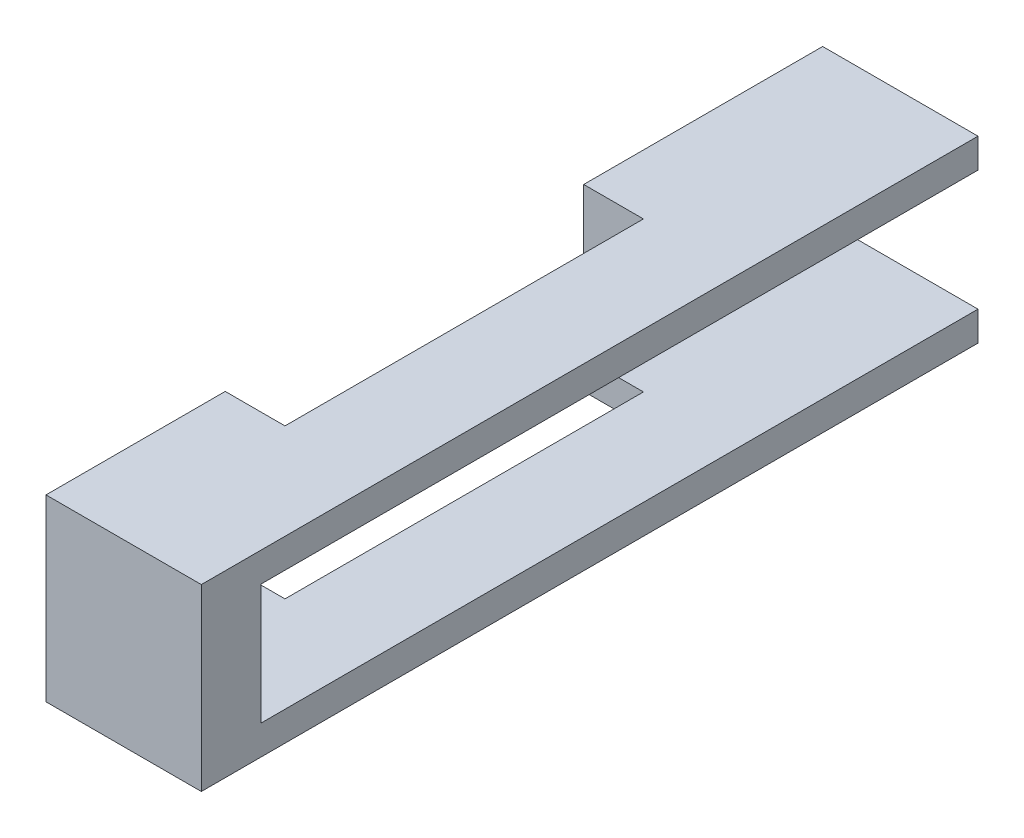
SolidWorks part; units mm, degrees
ref_plane "前视基准面" through (0, 0, 0) normal (0, 0, 1) x (1, 0, 0)
ref_plane "上视基准面" through (0, 0, 0) normal (0, 1, 0) x (1, 0, 0)
ref_plane "右视基准面" through (0, 0, 0) normal (1, 0, 0) x (0, 0, -1)
other "Configuration Table"
sketch "草图1" plane through (0, 0, 0) normal (0, 1, 0) x (1, 0, 0)
  line L1 (-15, 15) -> (15, 15)
  line L2 (-15, 15) -> (-15, -15)
  line L3 (-15, -15) -> (15, -15)
  line L4 (15, 15) -> (15, -15)
  line L5 (-15, 15) -> (15, -15) construction
  line L6 (-15, -15) -> (15, 15) construction
  point P0 (0, 0)
  dimension "D1" = 30
  dimension "D2" = 30
extrude "凸台-拉伸1" add sketch "草图1" along normal blind 30
sketch "草图2" plane through (15, 0, 0) normal (1, 0, 0) x (0, 0, -1)
  line L0 (15, 30) -> (15, 0) construction
  line L1 (-5, 4.975) -> (15, 4.975)
  line L2 (-5, 4.975) -> (-5, 25.025)
  line L3 (-5, 25.025) -> (15, 25.025)
  line L4 (15, 4.975) -> (15, 25.025)
  line L5 (-5, 4.975) -> (15, 25.025) construction
  line L6 (-5, 25.025) -> (15, 4.975) construction
  line L7 (-15, 15) -> (15, 15) construction
  line L9 (-15, 30) -> (-15, 0) construction
  point P0 (5, 15)
  dimension "D1" = 20.05
  dimension "D2" = 20
extrude "切除-拉伸1" cut sketch "草图2" against normal blind 20
sketch "草图3" plane through (-5, 0, 0) normal (1, 0, 0) x (0, 0, -1)
  line L0 (-5, 25.025) -> (15, 4.975)
  line L1 (15, 25.025) -> (-5, 4.975)
  circle A0 centre (5, 15) radius 3.1
  dimension "D1" = 6.2
extrude "切除-拉伸2" cut sketch "草图3" against normal blind 20 contours L0 A0 L1 | L1 A0 L0 | L0 A0 L1 | L1 A0 L0 region at (-5, 16.8613, -5) region at (-5, 15, -3.14) region at (-5, 15, -6.86) region at (-5, 13.1387, -5)
sketch "草图4" plane through (0, 0, 0) normal (0, -1, 0) x (1, 0, 0)
  line L0 (-10, -15) -> (-10, 15)
  line L4 (15, -15) -> (15, 15)
  line L5 (15, 15) -> (-15, 15)
  line L6 (-15, 15) -> (-15, -15)
  line L7 (-15, -15) -> (15, -15)
  line L8 (15, -15) -> (15, 15)
  line L9 (15, 15) -> (-15, 15)
  line L10 (-15, 15) -> (-15, -15)
  line L11 (-15, -15) -> (15, -15)
  line M7 (15, 15) -> (-15, 15)
  line M8 (-15, 15) -> (-15, -15)
  line M9 (-15, -15) -> (15, -15)
  dimension "D2" = 5
  dimension "D1" = 0
extrude "切除-拉伸3" cut sketch "草图4" against normal blind 55 contours L0 M9 M7 M8 region at (-12.5, 0, 0)
sketch "草图5" plane through (0, 0, -15) normal (0, 0, -1) x (-1, 0, 0)
  line L0 (-15, 30) -> (10, 30) construction
  line L1 (-15, 30) -> (0, 30)
  line L2 (-15, 30) -> (-15, 0)
  line L3 (-15, 0) -> (0, 0)
  line L4 (0, 30) -> (0, 0)
  line L5 (-15, 30) -> (0, 0) construction
  line L6 (-15, 0) -> (0, 30) construction
  line L7 (-15, 0) -> (10, 0) construction
  line L12 (-15, 25.025) -> (-15, 4.975)
  line L13 (-15, 4.975) -> (5, 4.975)
  line L14 (5, 4.975) -> (5, 25.025)
  line L15 (5, 25.025) -> (-15, 25.025)
  line L16 (-15, 25.025) -> (-15, 4.975)
  line L17 (-15, 4.975) -> (5, 4.975)
  line L18 (5, 4.975) -> (5, 25.025)
  line L19 (5, 25.025) -> (-15, 25.025)
  point P0 (-7.5, 15)
  line M6 (-15, 0) -> (10, 0)
  line M8 (10, 30) -> (-15, 30)
  line M9 (-15, 30) -> (-15, 25.025)
  line M10 (-15, 25.025) -> (5, 25.025)
  line M12 (5, 4.975) -> (-15, 4.975)
  line M13 (-15, 4.975) -> (-15, 0)
  dimension "D1" = 15
  dimension "D2" = 0
extrude "凸台-拉伸2" add sketch "草图5" along normal blind 120 contours L4 M8 M9 M10 | L4 M12 M13 M6 region at (7.5, 27.5125, -15) region at (7.5, 2.4875, -15)
sketch "草图6" plane through (0, 0, -135) normal (0, 0, -1) x (-1, 0, 0)
  line L1 (-15, 4.975) -> (5, 4.975)
  line L2 (-15, 4.975) -> (-15, 25.025)
  line L3 (-15, 25.025) -> (5, 25.025)
  line L4 (0, 0) -> (0, 4.975)
  line L5 (0, 4.975) -> (-15, 4.975)
  line L6 (-15, 4.975) -> (-15, 0)
  line L7 (-15, 0) -> (0, 0)
  line L8 (0, 0) -> (0, 4.975)
  line L9 (0, 4.975) -> (-15, 4.975)
  line L10 (-15, 4.975) -> (-15, 0)
  line L11 (-15, 0) -> (0, 0)
  line L12 (0, 25.025) -> (0, 30)
  line L13 (0, 30) -> (-15, 30)
  line L14 (-15, 30) -> (-15, 25.025)
  line L15 (-15, 25.025) -> (0, 25.025)
  line L16 (0, 25.025) -> (0, 30)
  line L17 (0, 30) -> (-15, 30)
  line L18 (-15, 30) -> (-15, 25.025)
  line L19 (-15, 25.025) -> (0, 25.025)
  line L20 (5, 4.975) -> (5, 25.025)
  line L21 (-15, 4.975) -> (5, 25.025) construction
  line L22 (-15, 25.025) -> (5, 4.975) construction
  line L23 (-15, 0) -> (10, 0)
  line L24 (-15, 0) -> (-15, 30)
  line L25 (-15, 30) -> (10, 30)
  line L26 (10, 0) -> (10, 30)
  line L27 (-15, 0) -> (10, 30) construction
  line L28 (-15, 30) -> (10, 0) construction
  point P6 (-5, 15)
  point P10 (-2.5, 15)
  line M11 (0, 0) -> (0, 4.975)
  dimension "D3" = 20
  dimension "D4" = 25
  dimension "D1" = 0
  dimension "D2" = 0
extrude "凸台-拉伸3" add sketch "草图6" against normal blind 60 contours L23 L26 L25 L16 L3 L20 L1 M11 region at (-6.2547, 15, -135)
sketch "草图7" plane through (-10, 0, 0) normal (-1, 0, 0) x (0, 0, 1)
  line L28 (5, 17.75) -> (-0.5279, 17.75)
  line L29 (-3.5647, 20.05) -> (-6.4353, 20.05)
  line L30 (-9.4721, 17.75) -> (-80.5279, 17.75)
  line L31 (-83.5647, 20.05) -> (-86.4353, 20.05)
  line L32 (-89.4721, 17.75) -> (-100.5279, 17.75)
  line L33 (-103.5647, 20.05) -> (-106.4353, 20.05)
  line L34 (-109.4721, 17.75) -> (-360.5279, 17.75)
  line L35 (-363.5647, 20.05) -> (-366.4353, 20.05)
  line L36 (-369.4721, 17.75) -> (-380.5279, 17.75)
  line L37 (-383.5647, 20.05) -> (-386.4353, 20.05)
  line L38 (-389.4721, 17.75) -> (-460.5279, 17.75)
  line L39 (-463.5647, 20.05) -> (-466.4353, 20.05)
  line L40 (-469.4721, 17.75) -> (-475, 17.75)
  line L41 (-475, 17.75) -> (-475, 12.25)
  line L42 (-475, 12.25) -> (-469.4721, 12.25)
  line L43 (-466.4353, 9.95) -> (-463.5647, 9.95)
  line L44 (-460.5279, 12.25) -> (-389.4721, 12.25)
  line L45 (-386.4353, 9.95) -> (-383.5647, 9.95)
  line L46 (-380.5279, 12.25) -> (-369.4721, 12.25)
  line L47 (-366.4353, 9.95) -> (-363.5647, 9.95)
  line L48 (-360.5279, 12.25) -> (-109.4721, 12.25)
  line L49 (-106.4353, 9.95) -> (-103.5647, 9.95)
  line L50 (-100.5279, 12.25) -> (-89.4721, 12.25)
  line L51 (-86.4353, 9.95) -> (-83.5647, 9.95)
  line L52 (-80.5279, 12.25) -> (-9.4721, 12.25)
  line L53 (-6.4353, 9.95) -> (-3.5647, 9.95)
  line L54 (-0.5279, 12.25) -> (5, 12.25)
  line L55 (5, 12.25) -> (5, 17.75)
  line L56 (5, 17.75) -> (-0.5279, 17.75)
  line L57 (-3.5647, 20.05) -> (-6.4353, 20.05)
  line L58 (-9.4721, 17.75) -> (-80.5279, 17.75)
  line L59 (-83.5647, 20.05) -> (-86.4353, 20.05)
  line L60 (-89.4721, 17.75) -> (-100.5279, 17.75)
  line L61 (-103.5647, 20.05) -> (-106.4353, 20.05)
  line L62 (-109.4721, 17.75) -> (-360.5279, 17.75)
  line L63 (-363.5647, 20.05) -> (-366.4353, 20.05)
  line L64 (-369.4721, 17.75) -> (-380.5279, 17.75)
  line L65 (-383.5647, 20.05) -> (-386.4353, 20.05)
  line L66 (-389.4721, 17.75) -> (-460.5279, 17.75)
  line L67 (-463.5647, 20.05) -> (-466.4353, 20.05)
  line L68 (-469.4721, 17.75) -> (-475, 17.75)
  line L69 (-475, 17.75) -> (-475, 12.25)
  line L70 (-475, 12.25) -> (-469.4721, 12.25)
  line L71 (-466.4353, 9.95) -> (-463.5647, 9.95)
  line L72 (-460.5279, 12.25) -> (-389.4721, 12.25)
  line L73 (-386.4353, 9.95) -> (-383.5647, 9.95)
  line L74 (-380.5279, 12.25) -> (-369.4721, 12.25)
  line L75 (-366.4353, 9.95) -> (-363.5647, 9.95)
  line L76 (-360.5279, 12.25) -> (-109.4721, 12.25)
  line L77 (-106.4353, 9.95) -> (-103.5647, 9.95)
  line L78 (-100.5279, 12.25) -> (-89.4721, 12.25)
  line L79 (-86.4353, 9.95) -> (-83.5647, 9.95)
  line L80 (-80.5279, 12.25) -> (-9.4721, 12.25)
  line L81 (-6.4353, 9.95) -> (-3.5647, 9.95)
  line L82 (-0.5279, 12.25) -> (5, 12.25)
  line L83 (5, 12.25) -> (5, 17.75)
  circle A7 centre (-105, 15) radius 3.1
  circle A8 centre (-85, 15) radius 3.1
  arc A31 (-0.5279, 17.75) -> (-3.5647, 20.05) centre (-5, 15) ccw
  arc A32 (-6.4353, 20.05) -> (-9.4721, 17.75) centre (-5, 15) ccw
  arc A33 (-80.5279, 17.75) -> (-83.5647, 20.05) centre (-85, 15) ccw
  arc A34 (-86.4353, 20.05) -> (-89.4721, 17.75) centre (-85, 15) ccw
  arc A35 (-100.5279, 17.75) -> (-103.5647, 20.05) centre (-105, 15) ccw
  arc A36 (-106.4353, 20.05) -> (-109.4721, 17.75) centre (-105, 15) ccw
  arc A37 (-360.5279, 17.75) -> (-363.5647, 20.05) centre (-365, 15) ccw
  arc A38 (-366.4353, 20.05) -> (-369.4721, 17.75) centre (-365, 15) ccw
  arc A39 (-380.5279, 17.75) -> (-383.5647, 20.05) centre (-385, 15) ccw
  arc A40 (-386.4353, 20.05) -> (-389.4721, 17.75) centre (-385, 15) ccw
  arc A41 (-460.5279, 17.75) -> (-463.5647, 20.05) centre (-465, 15) ccw
  arc A42 (-466.4353, 20.05) -> (-469.4721, 17.75) centre (-465, 15) ccw
  arc A43 (-469.4721, 12.25) -> (-466.4353, 9.95) centre (-465, 15) ccw
  arc A44 (-463.5647, 9.95) -> (-460.5279, 12.25) centre (-465, 15) ccw
  arc A45 (-389.4721, 12.25) -> (-386.4353, 9.95) centre (-385, 15) ccw
  arc A46 (-383.5647, 9.95) -> (-380.5279, 12.25) centre (-385, 15) ccw
  arc A47 (-369.4721, 12.25) -> (-366.4353, 9.95) centre (-365, 15) ccw
  arc A48 (-363.5647, 9.95) -> (-360.5279, 12.25) centre (-365, 15) ccw
  arc A49 (-109.4721, 12.25) -> (-106.4353, 9.95) centre (-105, 15) ccw
  arc A50 (-103.5647, 9.95) -> (-100.5279, 12.25) centre (-105, 15) ccw
  arc A51 (-89.4721, 12.25) -> (-86.4353, 9.95) centre (-85, 15) ccw
  arc A52 (-83.5647, 9.95) -> (-80.5279, 12.25) centre (-85, 15) ccw
  arc A53 (-9.4721, 12.25) -> (-6.4353, 9.95) centre (-5, 15) ccw
  arc A54 (-3.5647, 9.95) -> (-0.5279, 12.25) centre (-5, 15) ccw
  arc A55 (-0.5279, 17.75) -> (-3.5647, 20.05) centre (-5, 15) ccw
  arc A56 (-6.4353, 20.05) -> (-9.4721, 17.75) centre (-5, 15) ccw
  arc A57 (-80.5279, 17.75) -> (-83.5647, 20.05) centre (-85, 15) ccw
  arc A58 (-86.4353, 20.05) -> (-89.4721, 17.75) centre (-85, 15) ccw
  arc A59 (-100.5279, 17.75) -> (-103.5647, 20.05) centre (-105, 15) ccw
  arc A60 (-106.4353, 20.05) -> (-109.4721, 17.75) centre (-105, 15) ccw
  arc A61 (-360.5279, 17.75) -> (-363.5647, 20.05) centre (-365, 15) ccw
  arc A62 (-366.4353, 20.05) -> (-369.4721, 17.75) centre (-365, 15) ccw
  arc A63 (-380.5279, 17.75) -> (-383.5647, 20.05) centre (-385, 15) ccw
  arc A64 (-386.4353, 20.05) -> (-389.4721, 17.75) centre (-385, 15) ccw
  arc A65 (-460.5279, 17.75) -> (-463.5647, 20.05) centre (-465, 15) ccw
  arc A66 (-466.4353, 20.05) -> (-469.4721, 17.75) centre (-465, 15) ccw
  arc A67 (-469.4721, 12.25) -> (-466.4353, 9.95) centre (-465, 15) ccw
  arc A68 (-463.5647, 9.95) -> (-460.5279, 12.25) centre (-465, 15) ccw
  arc A69 (-389.4721, 12.25) -> (-386.4353, 9.95) centre (-385, 15) ccw
  arc A70 (-383.5647, 9.95) -> (-380.5279, 12.25) centre (-385, 15) ccw
  arc A71 (-369.4721, 12.25) -> (-366.4353, 9.95) centre (-365, 15) ccw
  arc A72 (-363.5647, 9.95) -> (-360.5279, 12.25) centre (-365, 15) ccw
  arc A73 (-109.4721, 12.25) -> (-106.4353, 9.95) centre (-105, 15) ccw
  arc A74 (-103.5647, 9.95) -> (-100.5279, 12.25) centre (-105, 15) ccw
  arc A75 (-89.4721, 12.25) -> (-86.4353, 9.95) centre (-85, 15) ccw
  arc A76 (-83.5647, 9.95) -> (-80.5279, 12.25) centre (-85, 15) ccw
  arc A77 (-9.4721, 12.25) -> (-6.4353, 9.95) centre (-5, 15) ccw
  arc A78 (-3.5647, 9.95) -> (-0.5279, 12.25) centre (-5, 15) ccw
  dimension "D2" = 6.2
  dimension "D1" = 0
extrude "切除-拉伸4" cut sketch "草图7" against normal blind 60 contours A8 region at (-10, 15, -85)
sketch "草图8" plane through (0, 0, -135) normal (0, 0, -1) x (-1, 0, 0)
  line L8 (-15.05, 25.075) -> (-15.05, 4.925)
  line L9 (-15.05, 4.925) -> (5.05, 4.925)
  line L10 (5.05, 4.925) -> (5.05, 25.075)
  line L11 (5.05, 25.075) -> (-15.05, 25.075)
  line L12 (-15.05, 25.075) -> (-15.05, 4.925)
  line L13 (-15.05, 4.925) -> (5.05, 4.925)
  line L14 (5.05, 4.925) -> (5.05, 25.075)
  line L15 (5.05, 25.075) -> (-15.05, 25.075)
  dimension "D1" = 0.05
extrude "切除-拉伸5" cut sketch "草图8" against normal up to surface (140 mm away) up to face at (5, 15, 5)
sketch "草图9" plane through (15, 0, 0) normal (1, 0, 0) x (0, 0, -1)
  line L8 (135, 4.925) -> (-5, 4.925)
  line L9 (-5, 4.925) -> (-5, 25.075)
  line L10 (-5, 25.075) -> (135, 25.075)
  line L11 (135, 25.075) -> (135, 30)
  line L12 (135, 30) -> (-15, 30)
  line L13 (-15, 30) -> (-15, 0)
  line L14 (-15, 0) -> (135, 0)
  line L15 (135, 0) -> (135, 4.925)
  line L16 (135, 4.925) -> (-5, 4.925)
  line L17 (-5, 4.925) -> (-5, 25.075)
  line L18 (-5, 25.075) -> (135, 25.075)
  line L19 (135, 25.075) -> (135, 30)
  line L20 (135, 30) -> (-15, 30)
  line L21 (-15, 30) -> (-15, 0)
  line L22 (-15, 0) -> (135, 0)
  line L23 (135, 0) -> (135, 4.925)
  dimension "D1" = 0
extrude "凸台-拉伸4" add sketch "草图9" along normal blind 1
sketch "草图10" plane through (-10, 0, 0) normal (-1, 0, 0) x (0, 0, 1)
  line L28 (5, 17.75) -> (-0.5279, 17.75)
  line L29 (-3.5647, 20.05) -> (-6.4353, 20.05)
  line L30 (-9.4721, 17.75) -> (-80.5279, 17.75)
  line L31 (-83.5647, 20.05) -> (-86.4353, 20.05)
  line L32 (-89.4721, 17.75) -> (-100.5279, 17.75)
  line L33 (-103.5647, 20.05) -> (-106.4353, 20.05)
  line L34 (-109.4721, 17.75) -> (-360.5279, 17.75)
  line L35 (-363.5647, 20.05) -> (-366.4353, 20.05)
  line L36 (-369.4721, 17.75) -> (-380.5279, 17.75)
  line L37 (-383.5647, 20.05) -> (-386.4353, 20.05)
  line L38 (-389.4721, 17.75) -> (-460.5279, 17.75)
  line L39 (-463.5647, 20.05) -> (-466.4353, 20.05)
  line L40 (-469.4721, 17.75) -> (-475, 17.75)
  line L41 (-475, 17.75) -> (-475, 12.25)
  line L42 (-475, 12.25) -> (-469.4721, 12.25)
  line L43 (-466.4353, 9.95) -> (-463.5647, 9.95)
  line L44 (-460.5279, 12.25) -> (-389.4721, 12.25)
  line L45 (-386.4353, 9.95) -> (-383.5647, 9.95)
  line L46 (-380.5279, 12.25) -> (-369.4721, 12.25)
  line L47 (-366.4353, 9.95) -> (-363.5647, 9.95)
  line L48 (-360.5279, 12.25) -> (-109.4721, 12.25)
  line L49 (-106.4353, 9.95) -> (-103.5647, 9.95)
  line L50 (-100.5279, 12.25) -> (-89.4721, 12.25)
  line L51 (-86.4353, 9.95) -> (-83.5647, 9.95)
  line L52 (-80.5279, 12.25) -> (-9.4721, 12.25)
  line L53 (-6.4353, 9.95) -> (-3.5647, 9.95)
  line L54 (-0.5279, 12.25) -> (5, 12.25)
  line L55 (5, 12.25) -> (5, 17.75)
  line L56 (5, 17.75) -> (-0.5279, 17.75)
  line L57 (-3.5647, 20.05) -> (-6.4353, 20.05)
  line L58 (-9.4721, 17.75) -> (-80.5279, 17.75)
  line L59 (-83.5647, 20.05) -> (-86.4353, 20.05)
  line L60 (-89.4721, 17.75) -> (-100.5279, 17.75)
  line L61 (-103.5647, 20.05) -> (-106.4353, 20.05)
  line L62 (-109.4721, 17.75) -> (-360.5279, 17.75)
  line L63 (-363.5647, 20.05) -> (-366.4353, 20.05)
  line L64 (-369.4721, 17.75) -> (-380.5279, 17.75)
  line L65 (-383.5647, 20.05) -> (-386.4353, 20.05)
  line L66 (-389.4721, 17.75) -> (-460.5279, 17.75)
  line L67 (-463.5647, 20.05) -> (-466.4353, 20.05)
  line L68 (-469.4721, 17.75) -> (-475, 17.75)
  line L69 (-475, 17.75) -> (-475, 12.25)
  line L70 (-475, 12.25) -> (-469.4721, 12.25)
  line L71 (-466.4353, 9.95) -> (-463.5647, 9.95)
  line L72 (-460.5279, 12.25) -> (-389.4721, 12.25)
  line L73 (-386.4353, 9.95) -> (-383.5647, 9.95)
  line L74 (-380.5279, 12.25) -> (-369.4721, 12.25)
  line L75 (-366.4353, 9.95) -> (-363.5647, 9.95)
  line L76 (-360.5279, 12.25) -> (-109.4721, 12.25)
  line L77 (-106.4353, 9.95) -> (-103.5647, 9.95)
  line L78 (-100.5279, 12.25) -> (-89.4721, 12.25)
  line L79 (-86.4353, 9.95) -> (-83.5647, 9.95)
  line L80 (-80.5279, 12.25) -> (-9.4721, 12.25)
  line L81 (-6.4353, 9.95) -> (-3.5647, 9.95)
  line L82 (-0.5279, 12.25) -> (5, 12.25)
  line L83 (5, 12.25) -> (5, 17.75)
  circle A2 centre (-5, 15) radius 5.25
  circle A3 centre (-105, 15) radius 5.25
  circle A4 centre (-85, 15) radius 5.25
  arc A27 (-0.5279, 17.75) -> (-3.5647, 20.05) centre (-5, 15) ccw
  arc A28 (-6.4353, 20.05) -> (-9.4721, 17.75) centre (-5, 15) ccw
  arc A29 (-80.5279, 17.75) -> (-83.5647, 20.05) centre (-85, 15) ccw
  arc A30 (-86.4353, 20.05) -> (-89.4721, 17.75) centre (-85, 15) ccw
  arc A31 (-100.5279, 17.75) -> (-103.5647, 20.05) centre (-105, 15) ccw
  arc A32 (-106.4353, 20.05) -> (-109.4721, 17.75) centre (-105, 15) ccw
  arc A33 (-360.5279, 17.75) -> (-363.5647, 20.05) centre (-365, 15) ccw
  arc A34 (-366.4353, 20.05) -> (-369.4721, 17.75) centre (-365, 15) ccw
  arc A35 (-380.5279, 17.75) -> (-383.5647, 20.05) centre (-385, 15) ccw
  arc A36 (-386.4353, 20.05) -> (-389.4721, 17.75) centre (-385, 15) ccw
  arc A37 (-460.5279, 17.75) -> (-463.5647, 20.05) centre (-465, 15) ccw
  arc A38 (-466.4353, 20.05) -> (-469.4721, 17.75) centre (-465, 15) ccw
  arc A39 (-469.4721, 12.25) -> (-466.4353, 9.95) centre (-465, 15) ccw
  arc A40 (-463.5647, 9.95) -> (-460.5279, 12.25) centre (-465, 15) ccw
  arc A41 (-389.4721, 12.25) -> (-386.4353, 9.95) centre (-385, 15) ccw
  arc A42 (-383.5647, 9.95) -> (-380.5279, 12.25) centre (-385, 15) ccw
  arc A43 (-369.4721, 12.25) -> (-366.4353, 9.95) centre (-365, 15) ccw
  arc A44 (-363.5647, 9.95) -> (-360.5279, 12.25) centre (-365, 15) ccw
  arc A45 (-109.4721, 12.25) -> (-106.4353, 9.95) centre (-105, 15) ccw
  arc A46 (-103.5647, 9.95) -> (-100.5279, 12.25) centre (-105, 15) ccw
  arc A47 (-89.4721, 12.25) -> (-86.4353, 9.95) centre (-85, 15) ccw
  arc A48 (-83.5647, 9.95) -> (-80.5279, 12.25) centre (-85, 15) ccw
  arc A49 (-9.4721, 12.25) -> (-6.4353, 9.95) centre (-5, 15) ccw
  arc A50 (-3.5647, 9.95) -> (-0.5279, 12.25) centre (-5, 15) ccw
  arc A51 (-0.5279, 17.75) -> (-3.5647, 20.05) centre (-5, 15) ccw
  arc A52 (-6.4353, 20.05) -> (-9.4721, 17.75) centre (-5, 15) ccw
  arc A53 (-80.5279, 17.75) -> (-83.5647, 20.05) centre (-85, 15) ccw
  arc A54 (-86.4353, 20.05) -> (-89.4721, 17.75) centre (-85, 15) ccw
  arc A55 (-100.5279, 17.75) -> (-103.5647, 20.05) centre (-105, 15) ccw
  arc A56 (-106.4353, 20.05) -> (-109.4721, 17.75) centre (-105, 15) ccw
  arc A57 (-360.5279, 17.75) -> (-363.5647, 20.05) centre (-365, 15) ccw
  arc A58 (-366.4353, 20.05) -> (-369.4721, 17.75) centre (-365, 15) ccw
  arc A59 (-380.5279, 17.75) -> (-383.5647, 20.05) centre (-385, 15) ccw
  arc A60 (-386.4353, 20.05) -> (-389.4721, 17.75) centre (-385, 15) ccw
  arc A61 (-460.5279, 17.75) -> (-463.5647, 20.05) centre (-465, 15) ccw
  arc A62 (-466.4353, 20.05) -> (-469.4721, 17.75) centre (-465, 15) ccw
  arc A63 (-469.4721, 12.25) -> (-466.4353, 9.95) centre (-465, 15) ccw
  arc A64 (-463.5647, 9.95) -> (-460.5279, 12.25) centre (-465, 15) ccw
  arc A65 (-389.4721, 12.25) -> (-386.4353, 9.95) centre (-385, 15) ccw
  arc A66 (-383.5647, 9.95) -> (-380.5279, 12.25) centre (-385, 15) ccw
  arc A67 (-369.4721, 12.25) -> (-366.4353, 9.95) centre (-365, 15) ccw
  arc A68 (-363.5647, 9.95) -> (-360.5279, 12.25) centre (-365, 15) ccw
  arc A69 (-109.4721, 12.25) -> (-106.4353, 9.95) centre (-105, 15) ccw
  arc A70 (-103.5647, 9.95) -> (-100.5279, 12.25) centre (-105, 15) ccw
  arc A71 (-89.4721, 12.25) -> (-86.4353, 9.95) centre (-85, 15) ccw
  arc A72 (-83.5647, 9.95) -> (-80.5279, 12.25) centre (-85, 15) ccw
  arc A73 (-9.4721, 12.25) -> (-6.4353, 9.95) centre (-5, 15) ccw
  arc A74 (-3.5647, 9.95) -> (-0.5279, 12.25) centre (-5, 15) ccw
  circle M2 centre (-85, 15) radius 3.1
  dimension "D1" = 10.5
  dimension "D3" = 10.5
  dimension "D2" = 0
extrude "切除-拉伸6" cut sketch "草图10" against normal blind 10 contours A3 L61 L77 | L61 A3 | L77 A3 | A4 L59 L79 M2 | L59 A4 | L79 A4 | A2 L57 L81 | L57 A2 | L81 A2 region at (-10, 15, -5) region at (-10, 20.1301, -5) region at (-10, 9.8699, -5) region at (-10, 16.3893, -80.0884) region at (-10, 20.1301, -85) region at (-10, 9.8699, -85) region at (-10, 15, -105) region at (-10, 20.1301, -105) region at (-10, 9.8699, -105)
sketch "草图11" plane through (0, 0, 0) normal (0, -1, 0) x (1, 0, 0)
  line L0 (0, -75) -> (0, -95)
  line L1 (0, -95) -> (-10, -95)
  line L8 (16, 15) -> (-10, 15)
  line L9 (-10, 15) -> (-10, -15)
  line L10 (-10, -15) -> (0, -15)
  line L11 (0, -15) -> (0, -75)
  line L12 (0, -75) -> (-10, -75)
  line L13 (-10, -75) -> (-10, -135)
  line L14 (-10, -135) -> (16, -135)
  line L15 (16, -135) -> (16, 15)
  line L16 (16, 15) -> (-10, 15)
  line L17 (-10, 15) -> (-10, -15)
  line L18 (-10, -15) -> (0, -15)
  line L19 (0, -15) -> (0, -75)
  line L20 (0, -75) -> (-10, -75)
  line L21 (-10, -75) -> (-10, -135)
  line L22 (-10, -135) -> (16, -135)
  line L23 (16, -135) -> (16, 15)
  dimension "D2" = 20
  dimension "D1" = 0
sketch "草图12" plane through (0, 0, 0) normal (0, -1, 0) x (1, 0, 0)
  line L0 (-10, -115) -> (16, -115)
  line L8 (16, 15) -> (-10, 15)
  line L9 (-10, 15) -> (-10, -15)
  line L10 (-10, -15) -> (0, -15)
  line L11 (0, -15) -> (0, -75)
  line L12 (0, -75) -> (-10, -75)
  line L13 (-10, -75) -> (-10, -135)
  line L14 (-10, -135) -> (16, -135)
  line L15 (16, -135) -> (16, 15)
  line L16 (16, 15) -> (-10, 15)
  line L17 (-10, 15) -> (-10, -15)
  line L18 (-10, -15) -> (0, -15)
  line L19 (0, -15) -> (0, -75)
  line L20 (0, -75) -> (-10, -75)
  line L21 (-10, -75) -> (-10, -135)
  line L22 (-10, -135) -> (16, -135)
  line L23 (16, -135) -> (16, 15)
  line M15 (-10, -75) -> (-10, -135)
  line M16 (-10, -135) -> (16, -135)
  line M17 (16, -135) -> (16, 15)
  dimension "D2" = 20
  dimension "D1" = 0
extrude "切除-拉伸8" cut sketch "草图12" against normal blind 87 contours L0 M15 M16 M17 region at (3, 0, -125)
